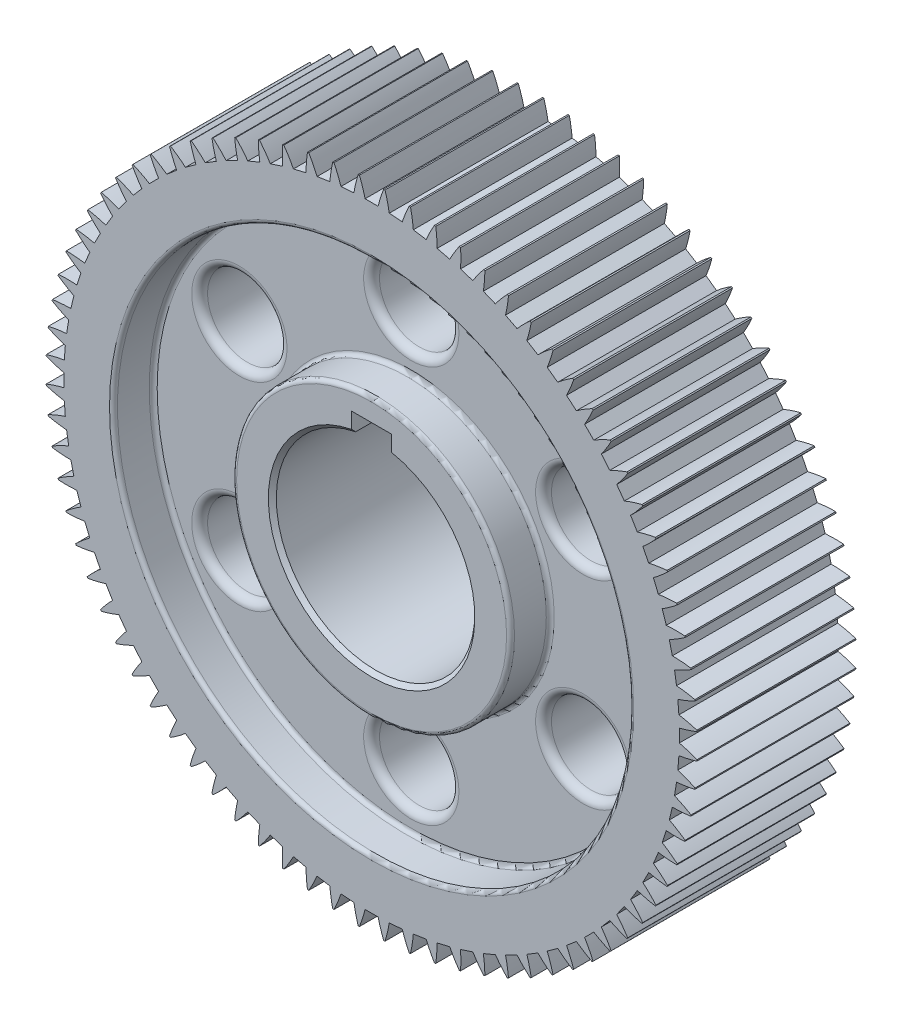
SolidWorks part; units mm, degrees
ref_plane "Front Plane" through (0, 0, 0) normal (0, 0, 1) x (1, 0, 0)
ref_plane "Top Plane" through (0, 0, 0) normal (0, 1, 0) x (1, 0, 0)
ref_plane "Right Plane" through (0, 0, 0) normal (1, 0, 0) x (0, 0, -1)
sketch "Sketch1" plane through (0, 0, 0) normal (0, 0, 1) x (1, 0, 0)
  circle A0 centre (0, 0) radius 80
  circle A1 centre (0, 0) radius 77.5
  circle A2 centre (0, 0) radius 82
  dimension "D1" = 164
  dimension "D2" = 160
  dimension "D3" = 155
extrude "Boss-Extrude1" add sketch "Sketch1" along normal blind 40 contours A2
sketch "Sketch3" plane through (0, 0, 40) normal (0, 0, 1) x (1, 0, 0)
  line L0 (0, 0) -> (0, -14.5028) construction
  line L1 (0, 0) -> (-0.7798, 39.7073) construction
  line L3 (3.0822, 82) -> (-3.0822, 82)
  line L4 (1.6357, 77.5) -> (-1.6357, 77.5)
  arc A0 (-1.6357, 77.5) -> (-3.0822, 82) centre (-34.379, 69.4574) ccw
  circle A1 centre (0, 0) radius 82 construction
  arc A2 (1.6357, 77.5) -> (3.0822, 82) centre (34.379, 69.4574) cw
  circle A5 centre (0, 0) radius 77.5 construction
  point P8 (0, 82)
  point P12 (0, 77.5)
  dimension "D1" = 1.125
extrude "Cut-Extrude1" cut sketch "Sketch3" against normal blind 70
pattern_circular "CirPattern1" count 80 over 360 about axis through (0, 0, 40) along (0, 0, 1) of "Cut-Extrude1"
sketch "Sketch4" plane through (0, 0, 40) normal (0, 0, 1) x (1, 0, 0)
  line L6 (-5, 24.4949) -> (-5, 29.4949)
  line L7 (-5, 29.4949) -> (5, 29.4949)
  line L8 (5, 24.4949) -> (5, 29.4949)
  arc A0 (-5, 24.4949) -> (5, 24.4949) centre (0, 0) ccw
  dimension "D1" = 50
  dimension "D2" = 5
  dimension "D3" = 10
  dimension "D4" = 5
extrude "Cut-Extrude2" cut sketch "Sketch4" against normal through all
sketch "Sketch5" plane through (0, 0, 40) normal (0, 0, 1) x (1, 0, 0)
  circle A0 centre (0, 0) radius 35
  circle A1 centre (0, 0) radius 65
  dimension "D1" = 70
  dimension "D2" = 130
extrude "Cut-Extrude3" cut sketch "Sketch5" against normal blind 10
extrude "Cut-Extrude4" cut sketch "Sketch5<2>" against normal blind 10 from offset 30 offset against normal yes
sketch "Sketch5<2>" plane through (0, 0, 40) normal (0, 0, 1) x (1, 0, 0) same geometry as "Sketch5"
sketch "Sketch6" plane through (0, 0, 30) normal (0, 0, 1) x (1, 0, 0)
  circle A0 centre (0, 50) radius 10
  dimension "D1" = 50
  dimension "20" = 20
extrude "Cut-Extrude5" cut sketch "Sketch6" against normal through all
pattern_circular "CirPattern2" count 6 over 360 about axis through (0, 0, 40) along (0, 0, 1) of "Cut-Extrude5"
chamfer "Chamfer1" distance 1 angle 45 1 edges at (0, -25, 40)
fillet "Fillet1" radius 1 4 edges at (35, 0, 10) (35, 0, 0) (35, 0, 40) (35, 0, 30)
fillet "Fillet2" radius 1 4 edges at (65, 0, 40) (65, 0, 30) (65, 0, 10) (65, 0, 0)
fillet "Fillet3" radius 2 12 edges at (53.3013, 25, 10) (48.3013, 16.3397, 30) (53.3013, -25, 10) (38.3013, -33.6603, 30) (10, -50, 10) (-10, -50, 30) (-33.3013, -25, 10) (-48.3013, -16.3397, 30) (-33.3013, 25, 10) (-38.3013, 33.6603, 30) (10, 50, 10) (10, 50, 30)
equation "\"module\"= 2"
equation "\"teeth\"= 80"
equation "\"D1@Sketch1\"=\"module\"*(\"teeth\"+2)"
equation "\"D2@Sketch1\"=\"module\"*\"teeth\""
equation "\"D3@Sketch1\"=\"module\"*(\"teeth\"-2.5)"
equation "\"D1@Sketch3\"=360/(\"teeth\"*4)"
equation "\"D1@CirPattern1\"=\"teeth\""
